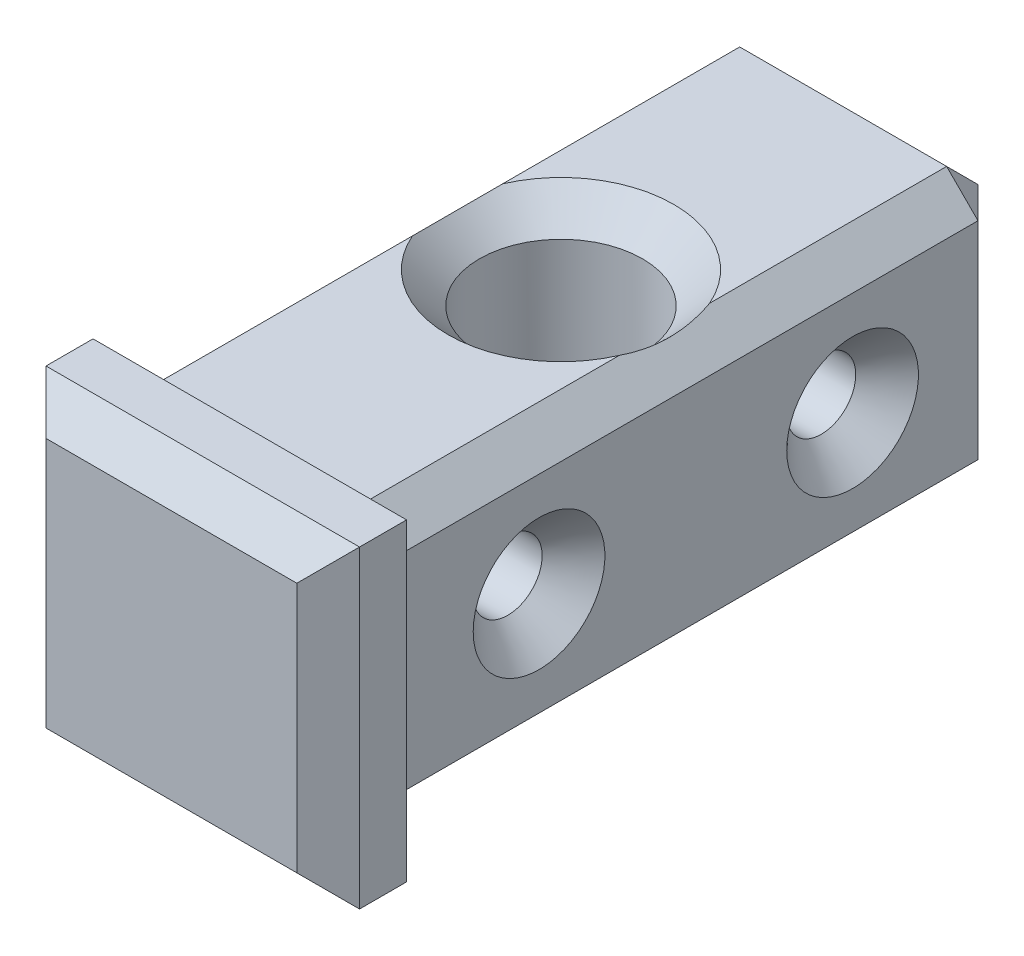
SolidWorks part; units mm, degrees
ref_plane "Front Plane" through (0, 0, 0) normal (0, 0, 1) x (1, 0, 0)
ref_plane "Top Plane" through (0, 0, 0) normal (0, 1, 0) x (1, 0, 0)
ref_plane "Right Plane" through (0, 0, 0) normal (1, 0, 0) x (0, 0, -1)
sketch "Sketch1" plane through (0, 0, 0) normal (0, 0, 1) x (1, 0, 0)
  line L22 (0, 0) -> (21.844, 0)
  line L23 (0, 0) -> (0, 21.844)
  line L24 (0, 21.844) -> (21.844, 21.844)
  line L25 (21.844, 0) -> (21.844, 21.844)
  point P4 (0, 0)
  point P5 (0, 0)
  point P18 (0, 0)
  dimension "D1" = 21.844
  dimension "D2" = 21.844
extrude "Boss-Extrude2" add sketch "Sketch1" along normal blind 50.8
sketch "Sketch2" plane through (0, 0, 50.8) normal (0, 0, 1) x (1, 0, 0)
  line L0 (0, 21.844) -> (0, 0) construction
  line L1 (-1.5875, -1.9685) -> (23.8125, -1.9685)
  line L2 (-1.5875, -1.9685) -> (-1.5875, 23.4315)
  line L3 (-1.5875, 23.4315) -> (23.8125, 23.4315)
  line L4 (23.8125, -1.9685) -> (23.8125, 23.4315)
  line L5 (21.844, 21.844) -> (0, 21.844) construction
  dimension "D1" = 25.4
  dimension "D2" = 1.5875
  dimension ".0625" = 1.5875
extrude "Boss-Extrude3" add sketch "Sketch2" along normal blind 6.35
sketch "Sketch4" plane through (0, 0, 0) normal (-1, 0, 0) x (0, 0, 1)
  line L0 (50.8, 21.844) -> (50.8, 0) construction
  line L2 (0, 10.922) -> (50.8, 10.922) construction
  line L3 (0, 21.844) -> (0, 0) construction
  circle A0 centre (38.1, 10.922) radius 2.794
  circle A1 centre (12.7, 10.922) radius 2.794
  point P8 (0, 0)
  dimension "D1" = 5.588
  dimension "D2" = 25.4
  dimension "D3" = 12.7
extrude "Cut-Extrude2" cut sketch "Sketch4" against normal through all
sketch "Sketch5" plane through (0, 21.844, 0) normal (0, 1, 0) x (1, 0, 0)
  line L0 (21.844, -50.8) -> (0, -50.8) construction
  line L1 (10.922, 0) -> (10.922, -50.8) construction
  line L2 (21.844, 0) -> (0, 0) construction
  circle A0 centre (10.922, -25.4) radius 6.604
  point P8 (0, 0)
  dimension "D1" = 13.208
  dimension "D2" = 25.4
extrude "Cut-Extrude3" cut sketch "Sketch5" against normal through all
chamfer "Chamfer2" distance 2.54 angle 45 18 edges at (10.922, 0, 32.004) (21.844, 10.922, 15.494) (21.844, 10.922, 40.894) (11.1125, -1.9685, 57.15) (23.8125, 10.7315, 57.15) (-1.5875, 10.7315, 57.15) (11.1125, 23.4315, 57.15) (0, 0, 25.4) (21.844, 0, 25.4) (21.844, 21.844, 25.4) (21.844, 10.922, 0) (10.922, 0, 0) (0, 10.922, 0) (10.922, 21.844, 0) (0, 21.844, 25.4) (0, 10.922, 40.894) (10.922, 21.844, 32.004) (0, 10.922, 15.494)
